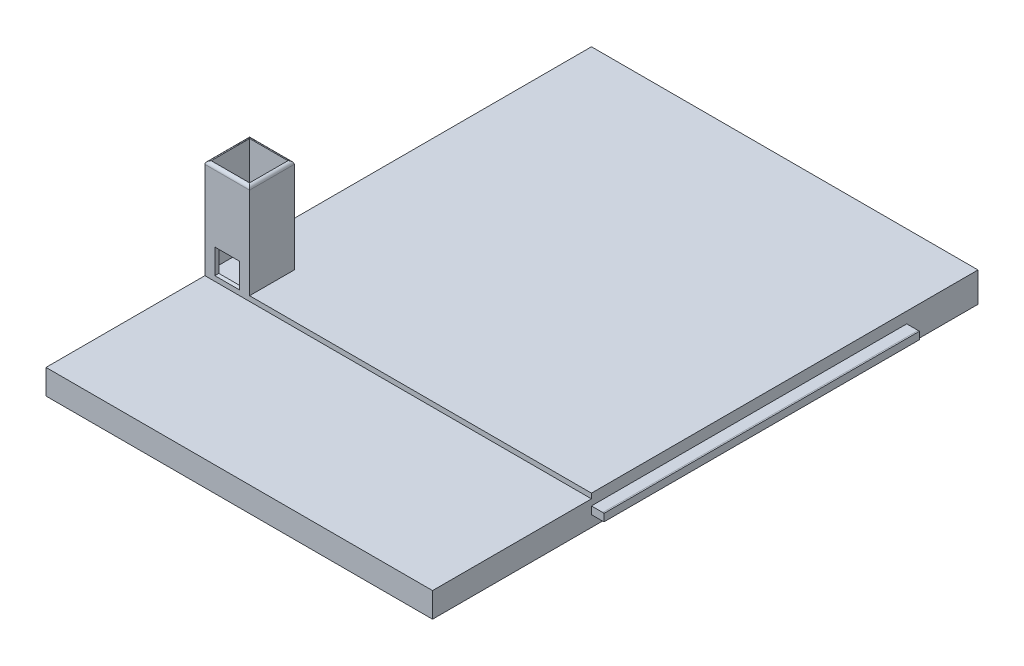
SolidWorks part; units mm, degrees
ref_plane "Front Plane" through (0, 0, 0) normal (0, 0, 1) x (1, 0, 0)
ref_plane "Top Plane" through (0, 0, 0) normal (0, 1, 0) x (1, 0, 0)
ref_plane "Right Plane" through (0, 0, 0) normal (1, 0, 0) x (0, 0, -1)
sketch "Sketch1" plane through (0, 0, 0) normal (0, 1, 0) x (1, 0, 0)
  line L1 (-22.3212, 15.875) -> (133.3788, 15.875)
  line L2 (-22.3212, 15.875) -> (-22.3212, -139.825)
  line L3 (-22.3212, -139.825) -> (133.3788, -139.825)
  line L4 (133.3788, 15.875) -> (133.3788, -139.825)
  line L5 (55.5288, -139.825) -> (55.5288, 15.875) construction
  line L6 (-22.3212, -61.975) -> (133.3788, -61.975) construction
  point P325 (-5.0492, -43.053)
  point P443 (-5.0492, -43.053)
  point P524 (55.5288, -61.975)
  dimension "D1" = 155.7
  dimension "D2" = 155.7
extrude "Boss-Extrude2" add sketch "Sketch1" along normal blind 12
sketch "Sketch2" plane through (0, 12, 0) normal (0, 1, 0) x (1, 0, 0)
  line L1 (-22.3212, -139.825) -> (-4.3212, -139.825)
  line L2 (-22.3212, -139.825) -> (-22.3212, -121.825)
  line L3 (-22.3212, -121.825) -> (-4.3212, -121.825)
  line L4 (-4.3212, -139.825) -> (-4.3212, -121.825)
  line L5 (-13.3212, -121.825) -> (-13.3212, -139.825) construction
  line L6 (-22.3212, -130.825) -> (-12.1612, -130.825) construction
  point P204 (-13.3212, -130.825)
  dimension "D1" = 18
  dimension "D2" = 18
extrude "Boss-Extrude3" add sketch "Sketch2" along normal blind 38.1
sketch "Sketch3" plane through (0, 0, 139.825) normal (0, 0, 1) x (1, 0, 0)
  line L0 (133.3788, 12) -> (133.3788, 0) construction
  line L1 (133.3788, 7.524) -> (138.4588, 7.524)
  line L2 (133.3788, 7.524) -> (133.3788, 4.476)
  line L3 (133.3788, 4.476) -> (138.4588, 4.476)
  line L4 (138.4588, 7.524) -> (138.4588, 4.476)
  line L5 (135.9188, 4.476) -> (135.9188, 7.524) construction
  line L6 (133.3788, 6) -> (138.4588, 6) construction
  line L7 (133.3788, 7.524) -> (133.3788, 12) construction
  line L8 (133.3788, 0) -> (135.9188, 4.476) construction
  line L9 (133.3788, 12) -> (135.9188, 7.524) construction
  point P1032 (135.9188, 6)
  dimension "D1" = 5.08
  dimension "D2" = 3.048
extrude "Boss-Extrude4" add sketch "Sketch3" against normal blind 127
chamfer "Chamfer1" distance 0.508 angle 4 1 edges at (138.4588, 7.524, 76.325) first distance on face at (135.9188, 7.524, 76.325)
chamfer "Chamfer2" distance 0.508 angle 4 1 edges at (138.4588, 4.476, 76.325) first distance on face at (135.9188, 4.476, 76.325)
sketch "Sketch4" plane through (-22.3212, 0, 0) normal (-1, 0, 0) x (0, 0, 1)
  line L0 (-15.875, 12) -> (-15.875, 0) construction
  line L1 (-15.875, 7.5875) -> (-10.541, 7.5875)
  line L2 (-15.875, 7.5875) -> (-15.875, 4.4125)
  line L3 (-15.875, 4.4125) -> (-10.541, 4.4125)
  line L4 (-10.541, 7.5875) -> (-10.541, 4.4125)
  line L5 (-13.208, 4.4125) -> (-13.208, 7.5875) construction
  line L6 (-15.875, 6) -> (-10.541, 6) construction
  line L7 (-15.875, 12) -> (-13.208, 7.5875) construction
  line L8 (-15.875, 0) -> (-13.208, 4.4125) construction
  point P456 (-13.208, 6)
  dimension "D1" = 5.334
  dimension "D2" = 3.175
  dimension "D3" = 5.1559
extrude "Cut-Extrude3" cut sketch "Sketch4" against normal blind 149.86 contours L2 L1 L4 L3
fillet "Fillet1" radius 1.27 4 edges at (-22.3212, 50.1, 130.825) (-13.3212, 50.1, 139.825) (-4.3212, 50.1, 130.825) (-13.3212, 50.1, 121.825) type face fillet first side face at (-13.3212, 50.1, 130.825) second side face at (-4.3212, 31.05, 130.825) second side face at (86.0875, 13.35, 139.825) second side face at (-22.3212, 14.82, 43.8718) second side face at (-13.3212, 31.05, 121.825)
sketch "Sketch5" plane through (0, 0, 0) normal (0, 1, 0) x (1, 0, 0)
  line L0 (-22.3212, -139.825) -> (-22.3212, -121.825) construction
  line L1 (133.3788, -139.825) -> (-22.3212, -139.825)
  line L2 (133.3788, -139.825) -> (133.3788, -203.825)
  line L3 (133.3788, -203.825) -> (-22.3212, -203.825)
  line L4 (-22.3212, -139.825) -> (-22.3212, -203.825)
  line L5 (55.5288, -203.825) -> (55.5288, -139.825) construction
  line L6 (133.3788, -171.825) -> (-22.3212, -171.825) construction
  point P2784 (55.5288, -171.825)
  dimension "D1" = 64
extrude "Boss-Extrude5" add sketch "Sketch5" along normal blind 10
sketch "Sketch6" plane through (0, 0, 139.825) normal (0, 0, 1) x (1, 0, 0)
  line L0 (-4.3212, 12) -> (133.3788, 12) construction
  line L1 (-8.3212, 12) -> (-18.3212, 12)
  line L2 (-8.3212, 12) -> (-8.3212, 22)
  line L3 (-8.3212, 22) -> (-18.3212, 22)
  line L4 (-18.3212, 12) -> (-18.3212, 22)
  line L5 (-13.3212, 27) -> (-13.3212, 12) construction
  line L6 (-8.3212, 17) -> (-18.3212, 17) construction
  line L7 (-4.3212, 48.83) -> (-22.3212, 48.83) construction
  line L8 (-13.3212, 27) -> (-13.3212, 48.83) construction
  point P4 (0, 0)
  point P7 (-13.3212, 48.83)
  point P408 (-13.3212, 17)
  dimension "D1" = 10
  dimension "D2" = 10
extrude "Cut-Extrude5" cut sketch "Sketch6" against normal blind 5 draft 15
sketch "Sketch8" plane through (0, 50.1, 0) normal (0, 1, 0) x (1, 0, 0)
  line L1 (-21.0512, -123.095) -> (-5.5912, -123.095)
  line L2 (-21.0512, -123.095) -> (-21.0512, -138.555)
  line L3 (-21.0512, -138.555) -> (-5.5912, -138.555)
  line L4 (-5.5912, -123.095) -> (-5.5912, -138.555)
  line L5 (-13.3212, -138.555) -> (-13.3212, -123.095) construction
  line L6 (-21.0512, -130.825) -> (-5.5912, -130.825) construction
  point P336 (-13.3212, -130.825)
extrude "Cut-Extrude6" cut sketch "Sketch8" against normal blind 38
